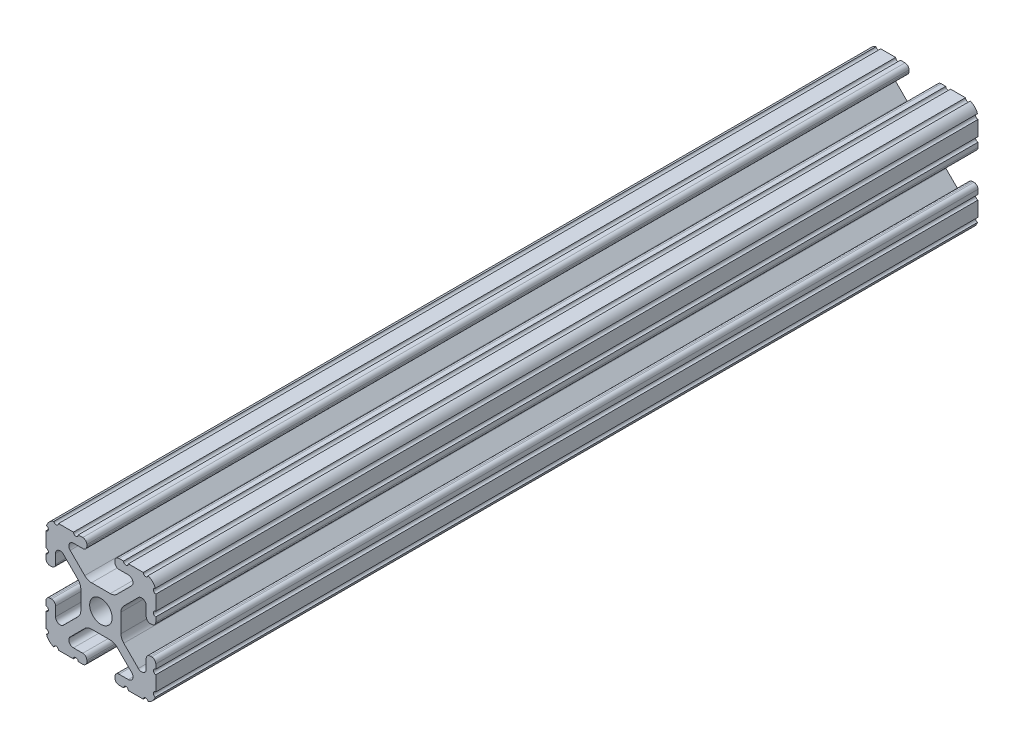
SolidWorks part; units mm, degrees
ref_plane "Front Plane" through (0, 0, 0) normal (0, 0, 1) x (1, 0, 0)
ref_plane "Top Plane" through (0, 0, 0) normal (0, 1, 0) x (1, 0, 0)
ref_plane "Right Plane" through (0, 0, 0) normal (1, 0, 0) x (0, 0, -1)
sketch "Sketch2" plane through (0, 0, 0) normal (0, 0, 1) x (1, 0, 0)
  line L0 (0, 12.7) -> (0, -12.7) construction
  line L1 (-12.7, 0) -> (12.7, 0) construction
  line L2 (3.2512, -12.7) -> (12.7, -12.7)
  line L3 (12.7, -12.7) -> (12.7, -3.2512)
  line L4 (3.2512, -12.7) -> (3.2512, -10.4902)
  line L5 (3.2512, -10.4902) -> (8.9276, -10.4902)
  line L6 (8.9276, -10.4902) -> (3.0856, -4.6482)
  line L7 (0, 0) -> (12.7, -12.7) construction
  line L8 (12.7, -3.2512) -> (10.4902, -3.2512)
  line L9 (10.4902, -3.2512) -> (10.4902, -8.9276)
  line L10 (10.4902, -8.9276) -> (4.6482, -3.0856)
  circle A0 centre (0, 0) radius 2.6035
  arc A1 (6.3485, -10.4902) -> (7.1039, -8.6665) centre (6.3485, -9.4219) ccw construction
  point P8 (0, -4.6482)
  dimension "Center Hole Diameter" = 5.207
  dimension "Rail Height" = 25.4
  dimension "Rail Width" = 25.4
  dimension "T-Slot Width" = 6.5024
  dimension "Slot Inner Width" = 14.8336
  dimension "Thickness" = 2.2098
  dimension "Slot Depth" = 5.842
  dimension "D1" = 2.2098
sketch "Sketch3" plane through (0, 0, 0) normal (1, 0, 0) x (0, 0, -1)
  line L0 (-95.123, -12.7) -> (95.123, -12.7) construction
  line L1 (-69.723, 0) -> (69.723, 0) construction
  line L2 (95.123, 0) -> (-95.123, 0) construction
sketch "Sketch4" plane through (0, 0, 0) normal (0, 0, 1) x (1, 0, 0)
  line L0 (4.1904, -12.7) -> (10.1173, -12.7)
  line L1 (3.2512, -12.7) -> (12.7, -12.7) construction
  line L2 (3.2512, -12.7) -> (3.2512, -10.4902) construction
  line L3 (3.2512, -10.4902) -> (8.9276, -10.4902) construction
  line L4 (3.2512, -11.4294) -> (3.2512, -11.7608)
  line L5 (4.1904, -10.4902) -> (6.3485, -10.4902)
  line L6 (0, -4.6482) -> (2.164, -4.6482)
  line L7 (8.9276, -10.4902) -> (3.0856, -4.6482) construction
  line L8 (3.7373, -5.2999) -> (7.1039, -8.6665)
  line L9 (12.7, -12.7) -> (12.7, -3.2512) construction
  line L10 (10.4902, -8.9276) -> (4.6482, -3.0856) construction
  line L11 (10.4902, -3.2512) -> (10.4902, -8.9276) construction
  line L12 (10.4902, -6.3485) -> (10.4902, -4.1904)
  line L13 (12.7, -3.2512) -> (10.4902, -3.2512) construction
  line L14 (11.4294, -3.2512) -> (11.7608, -3.2512)
  line L15 (12.7, -4.1904) -> (12.7, -10.1173)
  line L16 (8.6665, -7.1039) -> (5.2999, -3.7373)
  line L17 (4.6482, 0) -> (4.6482, -2.164)
  line L18 (-12.7, 0) -> (12.7, 0) construction
  line L19 (0, -4.6482) -> (0, -2.6035)
  line L20 (0, 12.7) -> (0, -12.7) construction
  line L21 (4.6482, 0) -> (2.6035, 0)
  arc A0 (3.2512, -11.7608) -> (4.1904, -12.7) centre (4.1904, -11.7608) ccw
  arc A2 (3.2512, -11.4294) -> (4.1904, -10.4902) centre (4.1904, -11.4294) cw
  arc A3 (6.3485, -10.4902) -> (7.1039, -8.6665) centre (6.3485, -9.4219) ccw
  arc A4 (2.164, -4.6482) -> (3.7373, -5.2999) centre (2.164, -6.8732) cw
  arc A5 (10.1173, -12.7) -> (12.7, -10.1173) centre (10.1173, -10.1173) ccw
  arc A6 (8.6665, -7.1039) -> (10.4902, -6.3485) centre (9.4219, -6.3485) ccw
  arc A7 (10.4902, -4.1904) -> (11.4294, -3.2512) centre (11.4294, -4.1904) cw
  arc A8 (11.7608, -3.2512) -> (12.7, -4.1904) centre (11.7608, -4.1904) cw
  arc A9 (5.2999, -3.7373) -> (4.6482, -2.164) centre (6.8732, -2.164) cw
  circle A10 centre (0, 0) radius 2.6035 construction
  arc A11 (0, -2.6035) -> (2.6035, 0) centre (0, 0) ccw
  dimension "D1" = 2.5827
  dimension "D2" = 2.225
  dimension "D3" = 0.9392
extrude "Boss-Extrude1" add sketch "Sketch4" along normal up to vertex (95.123 mm away) from vertex up to point (0, -12.7, 95.123) starting at point (0, -12.7, -95.123)
sketch "Sketch5" plane through (0, 0, 0) normal (0, 0, 1) x (1, 0, 0)
  line L0 (3.2512, -12.7) -> (12.7, -12.7) construction
  line L1 (4.1904, -10.4902) -> (6.3485, -10.4902) construction
  line L3 (0, 0) -> (12.7, -12.7) construction
  line L4 (6.3485, -10.4902) -> (6.3485, -12.7) construction
  line L5 (8.9276, -10.4902) -> (3.0856, -4.6482) construction
  circle A0 centre (10.3562, -12.7) radius 0.5524
  circle A1 centre (5.796, -12.7) radius 0.5524
  circle A2 centre (12.7, -10.3562) radius 0.5524
  circle A3 centre (12.7, -5.796) radius 0.5524
  point P10 (5.2694, -10.4902)
  point P12 (9.4219, -6.3485)
  dimension "D1" = 1.1049
extrude "Cut-Extrude1" cut sketch "Sketch5" against normal through all both and the other way through all
mirror "Mirror1" about plane through (0, 0, 0) normal (1, 0, 0) of bodies 137 134
mirror "Mirror2" about plane through (0, 0, 0) normal (0, 1, 0) of bodies 135
equation "\"D1@Sketch2\"=\"Thickness@Sketch2\""
equation "\"D2@Sketch4\"=\"Slot Inner Width@Sketch2\"*0.15"
equation "\"D1@Sketch4\"=\"D3@Sketch4\"*2.75"
equation "\"D3@Sketch4\"=\"Thickness@Sketch2\"*0.425"
equation "\"D1@Sketch5\"=\"Thickness@Sketch2\"*0.5"
equation "\"D1@Boss-Extrude1\"=\"Length@Sketch3\""
